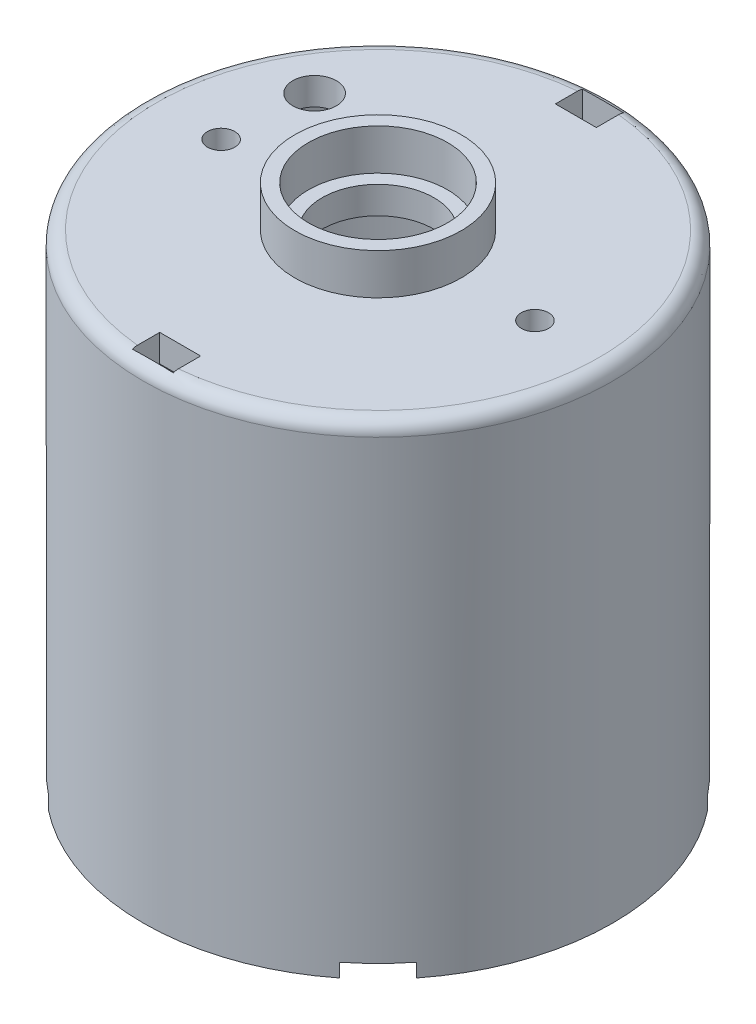
SolidWorks part; units mm, degrees
ref_plane "前基準面" through (0, 0, 0) normal (0, 0, 1) x (1, 0, 0)
ref_plane "上基準面" through (0, 0, 0) normal (0, 1, 0) x (1, 0, 0)
ref_plane "右基準面" through (0, 0, 0) normal (1, 0, 0) x (0, 0, -1)
sketch "草圖1" plane through (0, 0, 0) normal (0, 1, 0) x (1, 0, 0)
  circle A0 centre (0, 0) radius 8.6
  dimension "D1" = 17.2
extrude "伸長1" add sketch "草圖1" along normal blind 17.7
sketch "草圖2" plane through (0, 17.7, 0) normal (0, 1, 0) x (1, 0, 0)
  circle A0 centre (0, 0) radius 3.05
  circle A1 centre (0, 0) radius 2.55
  dimension "D1" = 6.1
  dimension "D2" = 0.5
extrude "伸長2" add sketch "草圖2" along normal blind 1.5
sketch "草圖3" [suppressed] plane through (0, 17.7, 0) normal (0, 1, 0) x (1, 0, 0)
  circle A1 centre (0, 0) radius 2.55
  circle A2 centre (0, 0) radius 2.55
  dimension "D1" = 0
shell "薄殼4" thickness 1 removed face at (0, 17.7, 2.55) removed face at (0, 0, 8.6)
sketch "草圖4" [suppressed] plane through (0, 17.7, 0) normal (0, 1, 0) x (1, 0, 0)
  circle A0 centre (0, 0) radius 2.55 construction
  circle A1 centre (0, 0) radius 2.55
extrude "伸長3" [suppressed] cut sketch "草圖4" against normal up to next
sketch "草圖5" plane through (0, 17.7, 0) normal (0, 1, 0) x (1, 0, 0)
  line L0 (-5.75, 0) -> (5.75, 0) construction
  line L1 (0, 7.75) -> (0, -7.75) construction
  line L2 (-0.75, 8.25) -> (0.75, 8.25)
  line L3 (-0.75, 8.25) -> (-0.75, 7.25)
  line L4 (-0.75, 7.25) -> (0.75, 7.25)
  line L5 (0.75, 8.25) -> (0.75, 7.25)
  line L6 (-0.75, 8.25) -> (0.75, 7.25) construction
  line L7 (-0.75, 7.25) -> (0.75, 8.25) construction
  line L8 (-0.75, -7.25) -> (0.75, -7.25)
  line L9 (-0.75, -7.25) -> (-0.75, -8.25)
  line L10 (-0.75, -8.25) -> (0.75, -8.25)
  line L11 (0.75, -7.25) -> (0.75, -8.25)
  line L12 (-0.75, -7.25) -> (0.75, -8.25) construction
  line L13 (-0.75, -8.25) -> (0.75, -7.25) construction
  line L14 (0, 0) -> (-5.5, 3.1754) construction
  circle A2 centre (-5.5, 3.1754) radius 0.8
  circle A3 centre (-5.75, 0) radius 0.5
  circle A4 centre (5.75, 0) radius 0.5
  point P5 (0, 7.75)
  point P10 (0, -7.75)
  dimension "D5" = 1
  dimension "D7" = 1.6
  dimension "D1" = 1
  dimension "D2" = 1.5
  dimension "D3" = 15.5
  dimension "D4" = 30
  dimension "D6" = 11.5
  dimension "D8" = 5.5
extrude "伸長5" cut sketch "草圖5" against normal blind 1.5
sketch "草圖7" plane through (0, 0, 0) normal (0, -1, 0) x (1, 0, 0)
  line L0 (0, 0) -> (-8.6, 0) construction
  line L1 (0, 0) -> (-10.9368, 10.9368) construction
  line L2 (-5.7629, 4.3487) -> (-6.965, 5.5508)
  line L3 (-5.7629, 4.3487) -> (-4.3487, 5.7629)
  line L4 (-6.965, 5.5508) -> (-5.5508, 6.965)
  line L5 (-4.3487, 5.7629) -> (-5.5508, 6.965)
  line L6 (-5.7629, 4.3487) -> (-5.5508, 6.965) construction
  line L7 (-6.965, 5.5508) -> (-4.3487, 5.7629) construction
  circle A0 centre (0, 0) radius 8.6 construction
  point P9 (-5.6569, 5.6569)
  dimension "D1" = 45
  dimension "D2" = 2
  dimension "D3" = 1.7
  dimension "D4" = 8
extrude "伸長6" cut sketch "草圖7" against normal blind 0.5
pattern_circular "環狀複製排列1" count 4 over 360 about axis through (0, 19.2, 0) along (0, -1, 0) of "伸長6"
fillet "圓角1" radius 0.5 1 edges at (0, 17.7, 8.6)
